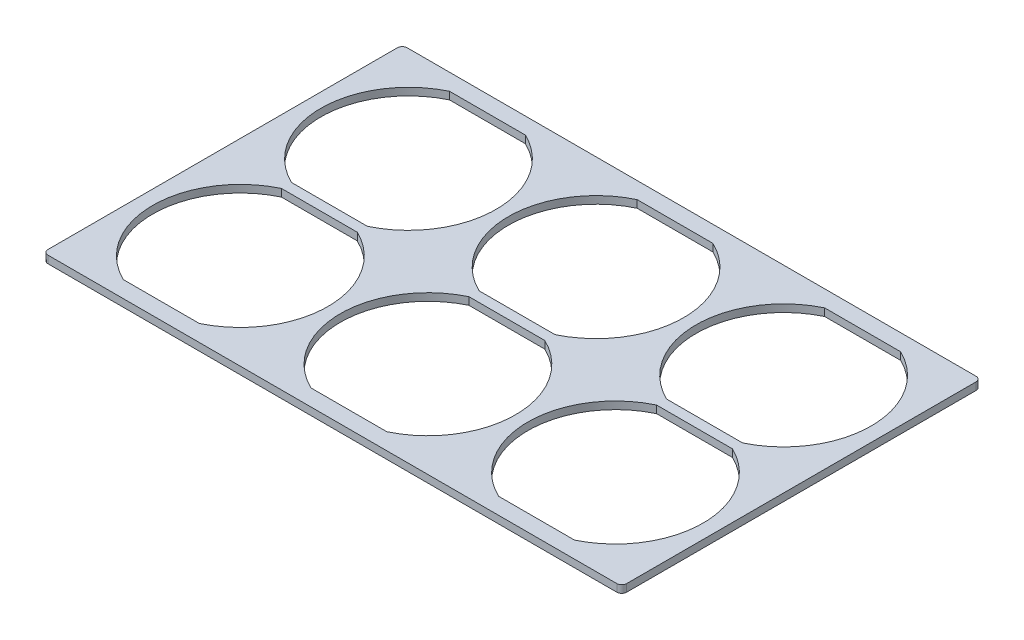
SolidWorks part; units mm, degrees
material "NEOPRENE"
ref_plane "Front" through (0, 0, 0) normal (0, 0, 1) x (1, 0, 0)
ref_plane "Top" through (0, 0, 0) normal (0, 1, 0) x (1, 0, 0)
ref_plane "Right" through (0, 0, 0) normal (1, 0, 0) x (0, 0, -1)
sketch "Sketch1" plane through (0, 0, 0) normal (0, 1, 0) x (1, 0, 0)
  line L0 (-24.1554, -3.2385) -> (24.1554, -3.2385)
  line L1 (-180.975, 114.3) -> (180.975, 114.3)
  line L2 (-184.15, 111.125) -> (-184.15, -111.125)
  line L3 (-180.975, -114.3) -> (180.975, -114.3)
  line L4 (184.15, 111.125) -> (184.15, -111.125)
  line L5 (-184.15, 114.3) -> (184.15, -114.3) construction
  line L6 (-184.15, -114.3) -> (184.15, 114.3) construction
  line L7 (95.2246, -3.2385) -> (143.5354, -3.2385)
  line L8 (95.2246, -3.2385) -> (95.2246, -103.7971) construction
  line L9 (95.2246, -103.7971) -> (143.5354, -103.7971)
  line L10 (143.5354, -3.2385) -> (143.5354, -103.7971) construction
  line L11 (95.2246, -3.2385) -> (143.5354, -103.7971) construction
  line L12 (95.2246, -103.7971) -> (143.5354, -3.2385) construction
  line L13 (-24.1554, -103.7971) -> (24.1554, -103.7971)
  line L14 (-143.5354, -3.2385) -> (-95.2246, -3.2385)
  line L15 (-143.5354, -103.7971) -> (-95.2246, -103.7971)
  line L16 (-24.1793, 103.7971) -> (24.1315, 103.7971)
  line L17 (-24.1793, 3.2385) -> (24.1315, 3.2385)
  line L18 (-143.5593, 103.7971) -> (-95.2485, 103.7971)
  line L19 (-143.5593, 3.2385) -> (-95.2485, 3.2385)
  line L20 (95.2007, 103.7971) -> (143.5115, 103.7971)
  line L21 (95.2007, 3.2385) -> (143.5115, 3.2385)
  line L22 (-95.2246, -103.7971) -> (-24.1554, -103.7971) construction
  line L23 (24.1554, -103.7971) -> (95.2246, -103.7971) construction
  arc A0 (95.2246, -3.2385) -> (95.2246, -103.7971) centre (119.4039, -53.5178) ccw
  arc A1 (143.5354, -3.2385) -> (143.5354, -103.7971) centre (119.3561, -53.5178) cw
  arc A2 (-184.15, -111.125) -> (-180.975, -114.3) centre (-180.975, -111.125) ccw
  arc A3 (184.15, -111.125) -> (180.975, -114.3) centre (180.975, -111.125) cw
  arc A4 (184.15, 111.125) -> (180.975, 114.3) centre (180.975, 111.125) ccw
  arc A5 (-180.975, 114.3) -> (-184.15, 111.125) centre (-180.975, 111.125) ccw
  circle A6 centre (119.38, 53.5178) radius 25.4 construction
  circle A7 centre (119.38, 53.5178) radius 25.4 construction
  circle A8 centre (0, 53.5178) radius 25.4 construction
  circle A9 centre (0, 53.5178) radius 25.4 construction
  arc A10 (-24.1554, -3.2385) -> (-24.1554, -103.7971) centre (0.0239, -53.5178) ccw
  arc A11 (24.1554, -3.2385) -> (24.1554, -103.7971) centre (-0.0239, -53.5178) cw
  arc A12 (-143.5354, -3.2385) -> (-143.5354, -103.7971) centre (-119.3561, -53.5178) ccw
  arc A13 (-95.2246, -3.2385) -> (-95.2246, -103.7971) centre (-119.4039, -53.5178) cw
  arc A14 (-24.1793, 103.7971) -> (-24.1793, 3.2385) centre (0, 53.5178) ccw
  arc A15 (24.1315, 103.7971) -> (24.1315, 3.2385) centre (-0.0478, 53.5178) cw
  arc A16 (-143.5593, 103.7971) -> (-143.5593, 3.2385) centre (-119.38, 53.5178) ccw
  arc A17 (-95.2485, 103.7971) -> (-95.2485, 3.2385) centre (-119.4278, 53.5178) cw
  arc A18 (95.2007, 103.7971) -> (95.2007, 3.2385) centre (119.38, 53.5178) ccw
  arc A19 (143.5115, 103.7971) -> (143.5115, 3.2385) centre (119.3322, 53.5178) cw
  circle A20 centre (-119.38, 53.5178) radius 25.4 construction
  point P0 (0, 0)
  point P6 (119.38, -53.5178)
  dimension "D4" = 111.5822
  dimension "D8" = 3.175
  dimension "D1" = 368.3
  dimension "D2" = 228.6
  dimension "D3" = 100.5586
  dimension "D5" = 48.3108
  dimension "D6" = 60.7822
  dimension "D7" = 64.77
  dimension "D13" = 119.38
  dimension "D11" = 3
  dimension "D12" = 2
extrude "Boss-Extrude1" add sketch "Sketch1" along normal blind 4.7752
